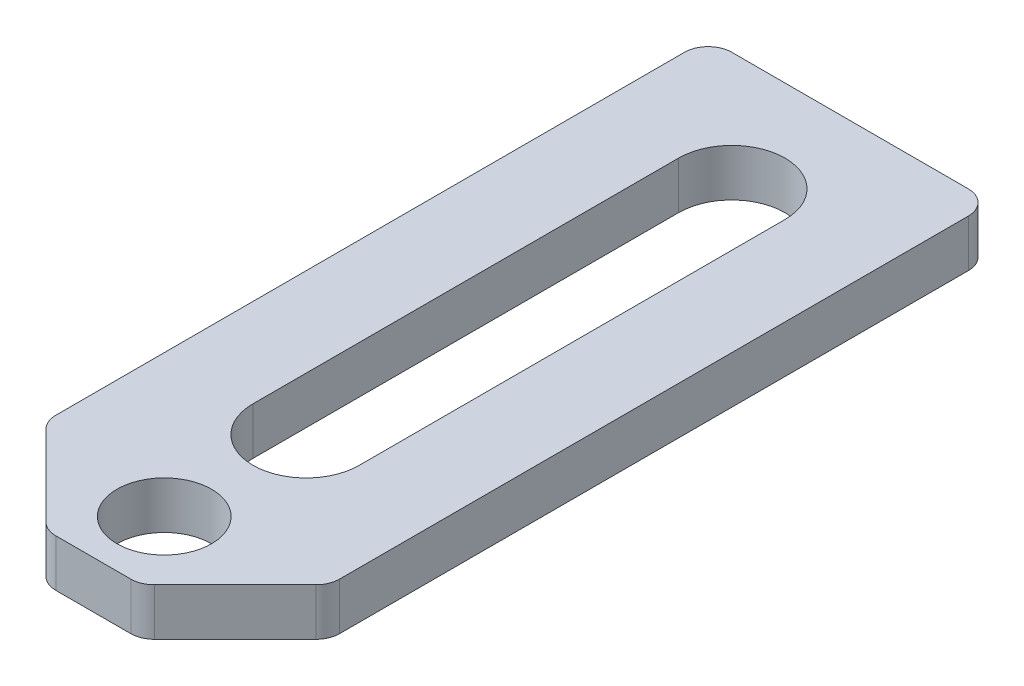
SolidWorks part; units mm, degrees
material "SS 304 (Default)"
ref_plane "Front Plane" through (0, 0, 0) normal (0, 0, 1) x (1, 0, 0)
ref_plane "Top Plane" through (0, 0, 0) normal (0, 1, 0) x (1, 0, 0)
ref_plane "Right Plane" through (0, 0, 0) normal (1, 0, 0) x (0, 0, -1)
sketch "Sketch1" plane through (0, 0, 0) normal (0, 0, 1) x (1, 0, 0)
  line L0 (-9.525, -1.5875) -> (9.525, 1.5875) construction
  line L1 (-9.525, 1.5875) -> (9.525, 1.5875)
  line L2 (-9.525, 1.5875) -> (-9.525, -1.5875)
  line L3 (-9.525, -1.5875) -> (9.525, -1.5875)
  line L4 (9.525, 1.5875) -> (9.525, -1.5875)
  dimension "D1" = 19.05
  dimension "D2" = 3.175
extrude "Extrude1" add sketch "Sketch1" along normal mid plane 50.8
sketch "Sketch2" plane through (0, 1.5875, 0) normal (0, 1, 0) x (-1, 0, 0)
  line L0 (3.5719, -17.4625) -> (3.5719, 11.1125)
  line L1 (-3.5719, -17.4625) -> (-3.5719, 11.1125)
  line L2 (-9.525, -25.4) -> (9.525, -25.4) construction
  line L3 (0, 11.1125) -> (0, -17.4625) construction
  arc A0 (3.5719, -17.4625) -> (-3.5719, -17.4625) centre (0, -17.4625) cw
  arc A1 (3.5719, 11.1125) -> (-3.5719, 11.1125) centre (0, 11.1125) ccw
  dimension "D2" = 28.575
  dimension "D1" = 7.9375
  dimension "D3" = 7.1437
extrude "Cut-Extrude1" cut sketch "Sketch2" against normal through all
chamfer "Chamfer1" distance 6.35 angle 45 2 edges at (-9.525, 0, 25.4) (9.525, 0, 25.4)
hole_wizard "1/4 (0.25) Diameter Hole1" positions "Sketch4" profile "Sketch3" hole size "1/4" standard "Ansi Inch" end condition through all
sketch "Sketch4" plane through (0, 1.5875, 0) normal (0, 1, 0) x (-1, 0, 0)
  line L0 (-3.175, 25.4) -> (3.175, 25.4) construction
  point P0 (0, 20.6375)
  dimension "D1" = 4.7625
sketch "Sketch3" plane through (0, 1.5875, 20.6375) normal (1, 0, 0) x (0, 0, 1)
  line L0 (0, 0) -> (0, 3.175)
  line L1 (0, 3.175) -> (3.175, 3.175)
  line L2 (3.175, 3.175) -> (3.175, 0)
  line L5 (3.175, 0) -> (0, 0)
  line L11 (0, -6.35) -> (0, 107.95) construction
  dimension "Thru Hole Dia." = 6.35
  dimension "Thru Hole Depth" = 3.175
fillet "Fillet1" radius 1.5875 6 edges at (-9.525, 0, -25.4) (9.525, 0, -25.4) (9.525, 0, 19.05) (3.175, 0, 25.4) (-3.175, 0, 25.4) (-9.525, 0, 19.05)
sheet metal parameters "Sheet-Metal1" parameters "D1"=1.5875
flatten bends "Flatten-Bends1" parameters "D1"=0
sketch "Sharp-Sketch1" plane through (0, 1.5875, 0) normal (0, 1, 0) x (-1, 0, 0)
process bends "Process-Bends1" parameters "D1"=0
sketch "Flat-Sketch1" plane through (0, 1.5875, 0) normal (0, 1, 0) x (-1, 0, 0)
